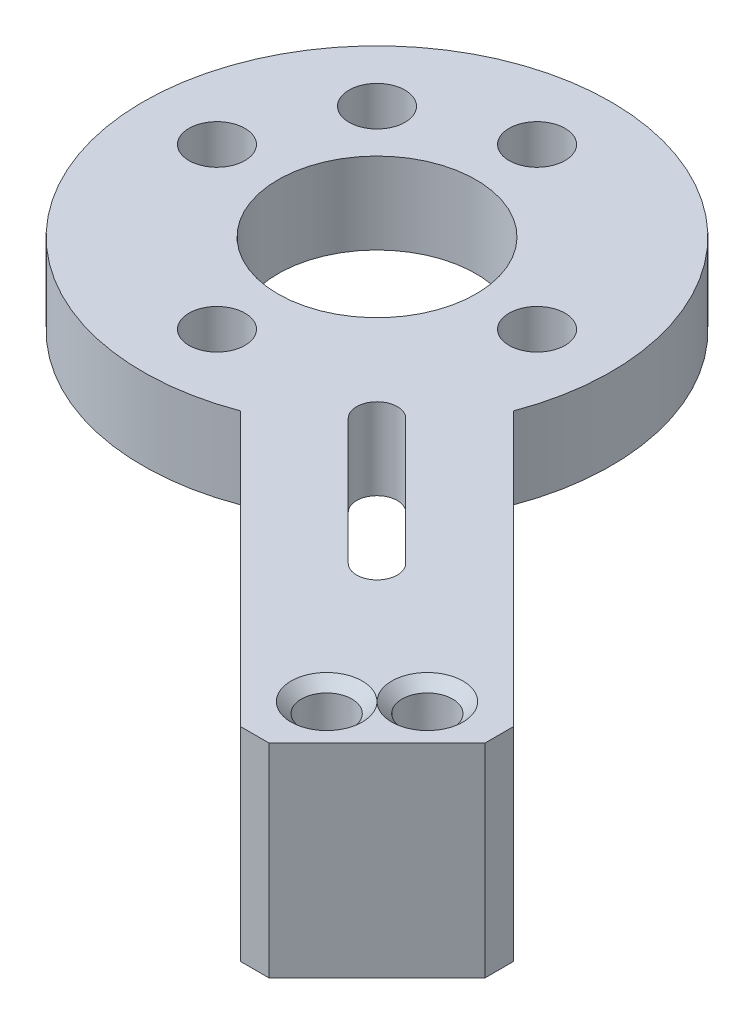
SolidWorks part; units mm, degrees
ref_plane "Front Plane" through (0, 0, 0) normal (0, 0, 1) x (1, 0, 0)
ref_plane "Top Plane" through (0, 0, 0) normal (0, 1, 0) x (1, 0, 0)
ref_plane "Right Plane" through (0, 0, 0) normal (1, 0, 0) x (0, 0, -1)
sketch "Sketch2" plane through (0, 0, 0) normal (0, 1, 0) x (1, 0, 0)
  line L0 (0, 0) -> (31.4663, 0) construction
  line L1 (15.7331, 0) -> (15.7331, 15.7331) construction
  line L2 (15.7331, 0) -> (4.6081, 11.125) construction
  line L3 (6, 0) -> (6, -5.038) construction
  line L4 (-6, 0) -> (-6, -5.038) construction
  line L5 (15.7331, 0) -> (58.8287, -43.0956) construction
  line L6 (58.8287, -43.0956) -> (65.5462, -36.3781)
  line L7 (65.5462, -36.3781) -> (37.262, -8.0938)
  line L8 (58.8287, -43.0956) -> (52.1112, -49.8131)
  line L9 (52.1112, -49.8131) -> (23.8269, -21.5288)
  line L10 (55.2932, -39.5601) -> (57.7681, -37.0852) construction
  line L11 (55.2932, -39.5601) -> (52.8183, -42.0349) construction
  line L12 (57.7681, -37.0852) -> (40.0904, -19.4075) construction
  circle A0 centre (0, 0) radius 2.75
  circle A1 centre (31.4663, 0) radius 2.75
  circle A2 centre (15.7331, 0) radius 15.7331 construction
  circle A3 centre (15.7331, 15.7331) radius 2.75
  circle A4 centre (15.7331, -15.7331) radius 2.75
  arc A5 (37.262, -8.0938) -> (23.8269, -21.5288) centre (15.7331, 0) ccw
  circle A6 centre (4.6081, 11.125) radius 2.75
  circle A9 centre (15.7331, 0) radius 9.7331
  dimension "D2" = 5.5
  dimension "D3" = 5.5
  dimension "D6" = 46
  dimension "D13" = 9.5
  dimension "D14" = 19
  dimension "D1" = 31.4663
  dimension "D4" = 45
  dimension "D5" = 22.25
  dimension "D7" = 6
  dimension "D8" = 6
  dimension "D9" = 7
  dimension "D10" = 3.5
  dimension "D11" = 40
  dimension "D12" = 5
extrude "Boss-Extrude1" add sketch "Sketch2" along normal blind 8
chamfer "Chamfer1" distance 2 angle 45 2 edges at (65.5462, 4, 36.3781) (52.1112, 4, 49.8131)
sketch "Sketch7" plane through (0, 0, 0) normal (0, -1, 0) x (-1, 0, 0)
  line L0 (-53.5254, -48.3989) -> (-64.132, -37.7923)
  line L1 (-64.132, -37.7923) -> (-64.132, -34.9639)
  line L2 (-64.132, -34.9639) -> (-56.016, -26.8479)
  line L3 (-65.5462, -36.3781) -> (-37.262, -8.0938) construction
  line L4 (-56.016, -26.8479) -> (-42.581, -40.2829)
  line L5 (-52.1112, -49.8131) -> (-23.8269, -21.5288) construction
  line L6 (-42.581, -40.2829) -> (-50.697, -48.3989)
  line L7 (-50.697, -48.3989) -> (-53.5254, -48.3989)
extrude "Boss-Extrude3" add sketch "Sketch7" along normal blind 12
ref_plane "Plane3" through (47.4266, 0, 47.4266) normal (0.7071, 0, 0.7071) x (0.7071, 0, -0.7071)
sketch "Sketch8" plane through (47.4266, 0, 47.4266) normal (0.7071, 0, 0.7071) x (0.7071, 0, -0.7071)
  line L0 (11.125, 0) -> (11.125, -12) construction
  line L1 (34.125, 0) -> (-11.875, 0) construction
  line L2 (18.625, -12) -> (3.625, -12) construction
  line L3 (7.625, 0) -> (7.625, -12) construction
  line L4 (14.625, 0) -> (14.625, -12) construction
  line L5 (5.525, -12) -> (5.125, 8)
  line L6 (3.625, 8) -> (18.625, 8) construction
  line L7 (5.125, 8) -> (7.625, 8)
  line L8 (7.625, 8) -> (7.625, -12)
  line L9 (7.625, -12) -> (5.525, -12)
  dimension "D1" = 3.5
  dimension "D2" = 3.5
  dimension "D3" = 2.1
  dimension "D4" = 2.5
revolve "Cut-Revolve2" cut sketch "Sketch8" angle 360 about L8
sketch "Sketch9" plane through (47.4266, 0, 47.4266) normal (0.7071, 0, 0.7071) x (0.7071, 0, -0.7071)
  line L0 (14.625, -12) -> (16.725, -12)
  line L1 (18.625, -12) -> (3.625, -12) construction
  line L2 (16.725, -12) -> (17.125, 8)
  line L3 (3.625, 8) -> (18.625, 8) construction
  line L4 (17.125, 8) -> (14.625, 8)
  line L5 (14.625, 8) -> (14.625, -12)
  dimension "D1" = 2.1
  dimension "D2" = 2.5
revolve "Cut-Revolve3" cut sketch "Sketch9" angle 360 about L5
chamfer "Chamfer2" distance 2 angle 45 1 edges at (49.2985, 0, 33.5654)
sketch "Sketch10" plane through (0, 0, 0) normal (0, -1, 0) x (1, 0, 0)
  line L0 (15.7331, 0) -> (58.8287, 43.0956) construction
  line L1 (29.7682, 16.8635) -> (42.1103, 29.2056)
  line L2 (44.8805, 26.3212) -> (32.8277, 14.3122)
  arc A0 (29.7682, 16.8635) -> (32.8277, 14.3122) centre (31.1824, 15.4493) ccw
  arc A1 (44.8805, 26.3212) -> (42.1103, 29.2056) centre (43.5245, 27.7914) ccw
  dimension "D1" = 2
extrude "Cut-Extrude2" cut sketch "Sketch10" against normal through all both and the other way through all
chamfer "Chamfer3" distance 1 angle 45 2 edges at (57.7681, 8, 39.5852) (52.8183, 8, 44.5349) first distance on face at (37.4155, 8, 21.6103)
